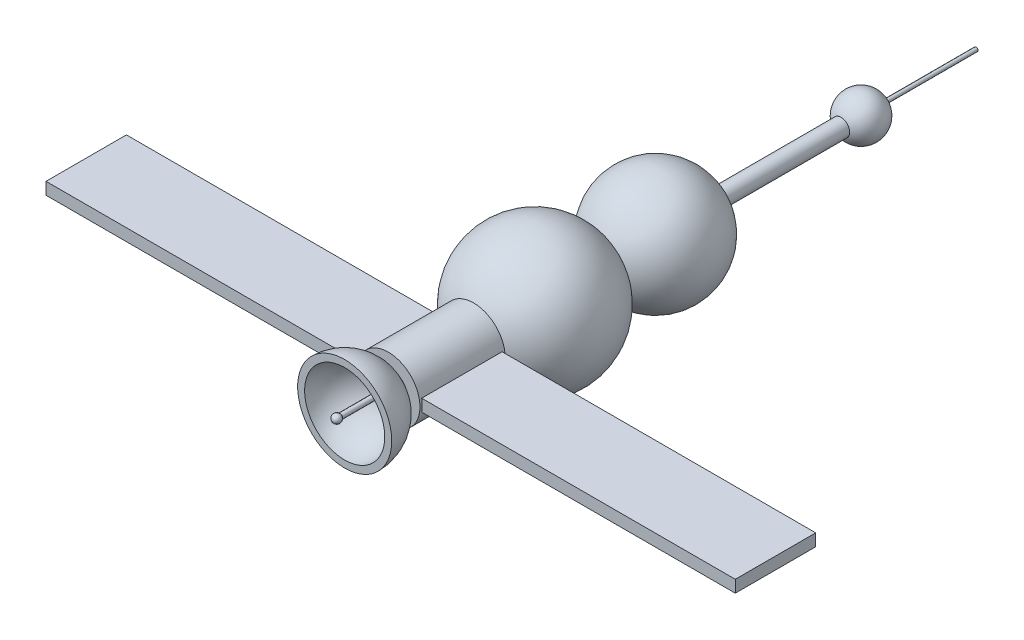
SolidWorks part; units mm, degrees
ref_plane "Front Plane" through (0, 0, 0) normal (0, 0, 1) x (1, 0, 0)
ref_plane "Top Plane" through (0, 0, 0) normal (0, 1, 0) x (1, 0, 0)
ref_plane "Right Plane" through (0, 0, 0) normal (1, 0, 0) x (0, 0, -1)
sketch "Sketch2" plane through (0, 0, 0) normal (0, 1, 0) x (1, 0, 0)
  line L0 (-10.4013, -42.0492) -> (-8.858, -42.0492)
  line L1 (-6.985, -13.208) -> (6.985, -13.208)
  line L2 (-6.985, -13.208) -> (-6.985, -32.3972)
  line L3 (-6.985, -32.3972) -> (-3.8764, -32.3972)
  line L4 (6.985, -13.208) -> (6.985, -32.3972)
  line L5 (8.858, -42.0492) -> (10.4013, -42.0492)
  line L6 (0, 98.6353) -> (0, -45.6163) construction
  line L8 (-0.5715, -33.2097) -> (-0.5715, -43.075)
  line L9 (-0.5715, -43.075) -> (0.5715, -43.075)
  line L10 (0.5715, -33.2097) -> (0.5715, -43.075)
  line L11 (-1.905, 34.6627) -> (1.905, 34.6627)
  line L12 (-1.905, 34.6627) -> (-1.905, 67.6827)
  line L13 (-1.905, 67.6827) -> (1.905, 67.6827)
  line L14 (1.905, 34.6627) -> (1.905, 67.6827)
  line L15 (-0.4322, 74.0347) -> (0.4322, 74.0347)
  line L16 (-0.4322, 74.0347) -> (-0.4322, 97.5407)
  line L17 (-0.4322, 97.5407) -> (0.4322, 97.5407)
  line L18 (0.4322, 74.0347) -> (0.4322, 97.5407)
  line L19 (3.8764, -32.3972) -> (6.985, -32.3972)
  arc A0 (6.985, -13.545) -> (-6.985, -13.545) centre (0, 0) ccw
  circle A1 centre (0, 26.67) radius 12.7
  arc A2 (-10.4013, -42.0492) -> (-3.8764, -32.3972) centre (0, -42.0492) cw
  arc A3 (8.858, -42.0492) -> (-8.858, -42.0492) centre (0, -42.0492) ccw
  circle A5 centre (0, 72.1171) radius 4.8263
  arc A6 (3.8764, -32.3972) -> (10.4013, -42.0492) centre (0, -42.0492) cw
  circle A7 centre (0, -43.8081) radius 0.9296
  point P12 (0, -13.208)
  point P18 (0, 67.6827)
  point P28 (0, 34.6627)
  point P35 (0, 74.0347)
  dimension "D2" = 9.652
  dimension "D3" = 25.4
  dimension "D4" = 30.48
  dimension "D5" = 26.67
  dimension "D16" = 9.6526
  dimension "D1" = 13.208
  dimension "D6" = 0
  dimension "D7" = 0
  dimension "D8" = 0
  dimension "D13" = 0
  dimension "D14" = 33.02
  dimension "D15" = 3.81
  dimension "D17" = 0
  dimension "D18" = 13.97
revolve "Revolve3" add sketch "Sketch2" angle 360 about L6 region at (-3.9162, 0, 24.654) region at (-0.2866, 0, 38.0693) region at (-0.2177, 0, 42.9956) region at (-0.4051, 0, 43.8567) region at (-6.6244, 0, -0.2665) region at (-5.6098, 0, -26.4661) region at (-1.5594, 0, -14.6167) region at (-0.9555, 0, -53.3709) region at (-2.1335, 0, -72.062) region at (-0.2161, 0, -87.2388) reverse direction yes
sketch "Sketch5" plane through (0, 0, 0) normal (1, 0, 0) x (0, 0, -1)
  line L1 (-31.8892, 1.3365) -> (-14.1092, 1.3365)
  line L2 (-31.8892, 1.3365) -> (-31.8892, -1.3365)
  line L3 (-31.8892, -1.3365) -> (-14.1092, -1.3365)
  line L4 (-14.1092, 1.3365) -> (-14.1092, -1.3365)
  line L6 (16.764, 0) -> (-16.764, 0) construction
  line L8 (-32.3972, 6.985) -> (-32.3972, -6.985) construction
  point P4 (-22.9992, 1.3365)
  point P8 (-31.8892, 0)
  dimension "D1" = 0
  dimension "D2" = 17.78
  dimension "D3" = 9.398
extrude "Boss-Extrude1" add sketch "Sketch5" along normal blind 76.2 and the other way blind 76.2
